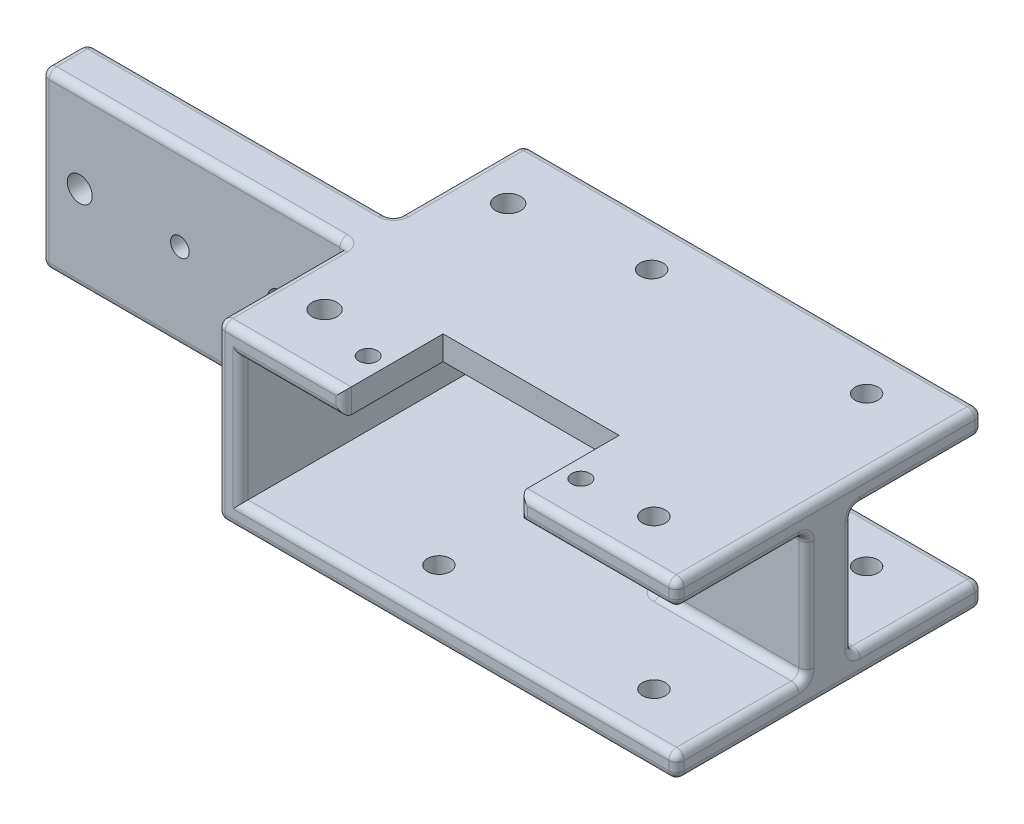
SolidWorks part; units mm, degrees
note: The reader was unsure of these and kept them because the rebuilt part matched: shared geometry of "Sketch1<2>".
ref_plane "Front Plane" through (0, 0, 0) normal (0, 0, 1) x (1, 0, 0)
ref_plane "Top Plane" through (0, 0, 0) normal (0, 1, 0) x (1, 0, 0)
ref_plane "Right Plane" through (0, 0, 0) normal (1, 0, 0) x (0, 0, -1)
sketch "Sketch1" plane through (0, 0, 0) normal (0, 1, 0) x (1, 0, 0)
  line L1 (0, 20) -> (60, 20)
  line L2 (0, 20) -> (0, -20)
  line L3 (0, -20) -> (60, -20)
  line L4 (60, 20) -> (60, -20)
  point P4 (0, 0)
  dimension "D1" = 60
  dimension "D2" = 40
extrude "Boss-Extrude1" add sketch "Sketch1" against normal blind 3.15
extrude "Boss-Extrude2" add sketch "Sketch1<2>" along normal blind 3.15 from offset 16.4 separate body
sketch "Sketch1<2>" plane through (0, 0, 0) normal (0, 1, 0) x (1, 0, 0) same geometry as "Sketch1"
sketch "Sketch2" plane through (0, 0, 0) normal (0, 1, 0) x (1, 0, 0)
  line L0 (0, -20) -> (60, -20) construction
  line L1 (0, 20) -> (3, 20)
  line L2 (0, 20) -> (0, -20)
  line L3 (0, -20) -> (3, -20)
  line L4 (3, 20) -> (3, -20)
  line L5 (60, -20) -> (60, 20) construction
  line L6 (60, 3) -> (40, 3)
  line L7 (60, 3) -> (60, -3)
  line L8 (60, -3) -> (40, -3)
  line L9 (40, 3) -> (40, -3)
  point P14 (60, 0)
  dimension "D2" = 6
  dimension "D3" = 20
extrude "Boss-Extrude3" add sketch "Sketch2" along normal up to surface (16.4 mm away) up to face at (30, 16.4, 0)
sketch "Sketch3" plane through (0, 0, 0) normal (-1, 0, 0) x (0, 0, 1)
  line L0 (-20, 19.55) -> (20, 19.55) construction
  line L1 (-3, 19.55) -> (3, 19.55)
  line L2 (-3, 19.55) -> (-3, -3.15)
  line L3 (-3, -3.15) -> (3, -3.15)
  line L4 (3, 19.55) -> (3, -3.15)
  line L5 (-20, -3.15) -> (20, -3.15) construction
  point P8 (0, 19.55)
  dimension "D3" = 6
extrude "Boss-Extrude4" add sketch "Sketch3" along normal blind 40
hole_wizard "M2 Clearance Hole1" positions "Sketch7" profile "Sketch9" hole size "M2" standard "ANSI Metric"
sketch "Sketch7" plane through (0, 19.55, 0) normal (0, 1, 0) x (1, 0, 0)
  line L1 (0, -20) -> (60, -20) construction
  line L2 (60, -20) -> (60, 20) construction
  point P0 (14.1, -14.4)
  point P2 (41.9, -14.4)
  point P5 (14.1, -14.4)
  point P7 (41.9, -14.4)
  dimension "D1" = 27.8
  dimension "D3" = 5.6
  dimension "D2" = 18.1
sketch "Sketch9" plane through (14.1, 19.55, 14.4) normal (1, 0, 0) x (0, 0, 1)
  line L0 (0, 0) -> (0, 5.721)
  line L1 (0, 5.721) -> (1.2, 5)
  line L2 (1.2, 5) -> (1.2, 0)
  line L5 (1.2, 0) -> (0, 0)
  line L10 (0, 5.721) -> (-1.2, 5) construction
  line L11 (0, -6.35) -> (0, 107.95) construction
  dimension "Hole Dia." = 2.4
  dimension "Hole Depth" = 5
  dimension "Drill Angle" = 118
hole_wizard "Ø3.0mm Dowel Hole1" positions "Sketch10" profile "Sketch11" hole size "Ø3.0" standard "ANSI Metric" end condition through all
sketch "Sketch10" plane through (0, 19.55, 0) normal (0, 1, 0) x (1, 0, 0)
  line L0 (0, -20) -> (60, -20) construction
  line L1 (60, -20) -> (60, 20) construction
  point P0 (50.95, -13.9)
  point P7 (22.85, 13.9)
  point P13 (50.95, 13.9)
  point P14 (22.85, -13.9)
  dimension "D1" = 6.1
  dimension "D2" = 9.05
  dimension "D4" = 37.15
  dimension "D3" = 27.8
sketch "Sketch11" plane through (50.95, 19.55, 13.9) normal (1, 0, 0) x (0, 0, 1)
  line L0 (0, 0) -> (0, 22.7)
  line L1 (0, 22.7) -> (1.5, 22.7)
  line L2 (1.5, 22.7) -> (1.5, 0)
  line L5 (1.5, 0) -> (0, 0)
  line L11 (0, -6.35) -> (0, 107.95) construction
  dimension "Thru Hole Dia." = 3
  dimension "Thru Hole Depth" = 22.7
sketch "Sketch5" plane through (0, 19.55, 0) normal (0, 1, 0) x (1, 0, 0)
  line L0 (0, -20) -> (60, -20) construction
  line L1 (16.5, -20) -> (39.5, -20)
  line L2 (16.5, -20) -> (16.5, -7)
  line L3 (16.5, -7) -> (39.5, -7)
  line L4 (39.5, -20) -> (39.5, -7)
  circle A0 centre (41.9, -14.4) radius 1.2 construction
  point P6 (28, -7)
  dimension "D1" = 23
  dimension "D2" = 13.9
  dimension "D3" = 13
extrude "Cut-Extrude1" cut sketch "Sketch5" against normal blind 7
fillet "Fillet1" radius 1 50 edges at (60, -3.15, 0) (49.75, 19.55, 20) (49.75, 16.4, 20) (16.5, 17.975, 20) (39.5, 17.975, 20) (30, -3.15, -20) (31.5, 0, 20) (3, 8.2, 20) (3, 8.2, -20) (9.75, 16.4, 20) (60, 16.4, 11.5) (60, 17.975, 20) (31.5, 16.4, -20) (60, 17.975, -20) (0, 19.55, -11.5) (8.25, 19.55, 20) (60, 19.55, 0) (30, 19.55, -20) (60, 16.4, -11.5) (60, 0, -11.5) (60, 8.2, 3) (60, 8.2, -3) (50, 0, -3) (40, 8.2, -3) (40, 0, 0) (40, 8.2, 3) (50, 0, 3) (50, 16.4, 3) (50, 16.4, -3) (40, 16.4, 0) (0, -3.15, -11.5) (31.5, 0, -20) (0, 19.55, 11.5) (0, -3.15, 11.5) (60, 0, 11.5) (0, 8.2, -3) (-20, 19.55, -3) (-20, -3.15, -3) (0, 8.2, 3) (-20, -3.15, 3) (-20, 19.55, 3) (-40, 8.2, -3) (-40, -3.15, 0) (-40, 8.2, 3) (-40, 19.55, 0) (30, -3.15, 20) (0, 8.2, -20) (60, -1.575, -20) (60, -1.575, 20) (0, 8.2, 20)
hole_wizard "#4 Clearance Hole1" positions "Sketch14" profile "Sketch15" hole size "#4" standard "ANSI Inch" end condition through all
sketch "Sketch14" plane through (0, 0, 3) normal (0, 0, 1) x (1, 0, 0)
  line L0 (-40, -2.15) -> (-40, 18.55) construction
  point P0 (-35, 8.2)
  point P2 (-8.82, 8.2)
  point P7 (-40, 8.2)
  dimension "D1" = 26.18
  dimension "D2" = 5
sketch "Sketch15" plane through (-35, 8.2, 3) normal (1, 0, 0) x (0, -1, 0)
  line L0 (0, 0) -> (0, 23)
  line L1 (0, 23) -> (1.6319, 23)
  line L2 (1.6319, 23) -> (1.6319, 0)
  line L5 (1.6319, 0) -> (0, 0)
  line L11 (0, -6.35) -> (0, 107.95) construction
  dimension "Thru Hole Dia." = 3.2639
  dimension "Thru Hole Depth" = 23
hole_wizard "#2 Clearance Hole1" positions "Sketch16" profile "Sketch17" hole size "#2" standard "ANSI Inch" end condition through all
sketch "Sketch16" plane through (0, 0, 3) normal (0, 0, 1) x (1, 0, 0)
  line L0 (-40, -2.15) -> (-40, 18.55) construction
  circle A0 centre (-35, 8.2) radius 1.632 construction
  point P0 (-21.91, 8.2)
  point P8 (-40, 8.2)
  dimension "D1" = 13.09
sketch "Sketch17" plane through (-21.91, 8.2, 3) normal (1, 0, 0) x (0, -1, 0)
  line L0 (0, 0) -> (0, 23)
  line L1 (0, 23) -> (1.2192, 23)
  line L2 (1.2192, 23) -> (1.2192, 0)
  line L5 (1.2192, 0) -> (0, 0)
  line L11 (0, -6.35) -> (0, 107.95) construction
  dimension "Thru Hole Dia." = 2.4384
  dimension "Thru Hole Depth" = 23
hole_wizard "#4 Clearance Hole2" positions "Sketch18" profile "Sketch19" hole size "#4" standard "ANSI Inch"
sketch "Sketch18" plane through (0, 19.55, 0) normal (0, 1, 0) x (1, 0, 0)
  point P0 (6, 12)
  point P2 (6, -12)
  point P6 (0, 0)
  dimension "D1" = 12
  dimension "D2" = 12
  dimension "D3" = 6
sketch "Sketch19" plane through (6, 19.55, -12) normal (1, 0, 0) x (0, 0, 1)
  line L0 (0, 0) -> (0, 10.9806)
  line L1 (0, 10.9806) -> (1.6319, 10)
  line L2 (1.6319, 10) -> (1.6319, 0)
  line L5 (1.6319, 0) -> (0, 0)
  line L10 (0, 10.9806) -> (-1.632, 10) construction
  line L11 (0, -6.35) -> (0, 107.95) construction
  dimension "Hole Dia." = 3.2639
  dimension "Hole Depth" = 10
  dimension "Drill Angle" = 118
equation "\"D2@Sketch7\"=9.05*2"
equation "\"D1@Sketch10\"=(40-\"D3@Sketch10\")/2"
equation "\"D3@Sketch7\"=5.6"
equation "\"D2@Sketch18\"=\"D1@Sketch18\""
